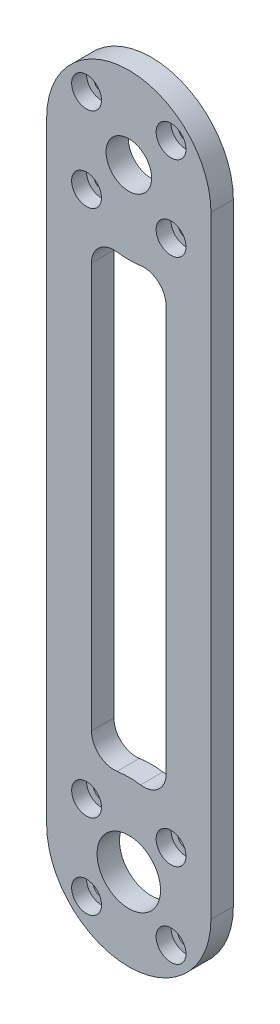
SolidWorks part; units mm, degrees
note: The reader was unsure of these and kept them because the rebuilt part matched: shared geometry of "Sketch3<6>", "Sketch2<5>".
ref_plane "Front Plane" through (0, 0, 0) normal (0, 0, 1) x (1, 0, 0)
ref_plane "Top Plane" through (0, 0, 0) normal (0, 1, 0) x (1, 0, 0)
ref_plane "Right Plane" through (0, 0, 0) normal (1, 0, 0) x (0, 0, -1)
sketch "Sketch1" plane through (0, 0, 0) normal (0, 0, 1) x (1, 0, 0)
  line L0 (0, 41) -> (0, -41) construction
  line L2 (11, 41) -> (11, -41)
  line L4 (-11, 41) -> (-11, -41)
  line L7 (-5, 31.202) -> (-5, -31.202)
  line L9 (5, 31.202) -> (5, -31.202)
  circle A0 centre (0, 41) radius 11
  circle A1 centre (0, -41) radius 11
  point P0 (0, 0)
  point P2 (0, 0)
  dimension "D3" = 22
  dimension "D1" = 82
  dimension "D5" = 6
  dimension "D2" = 22
  dimension "D6" = 6
extrude "Boss-Extrude1" add sketch "Sketch1" along normal blind 3
sketch "Sketch2" plane through (0, 0, 3) normal (0, 0, 1) x (1, 0, 0)
  line L0 (0, 41) -> (5.6569, 46.6569) construction
  line L1 (11, 41) -> (11, -41) construction
  circle A0 centre (0, 41) radius 3.05
  circle A1 centre (5.6569, 46.6569) radius 1
  circle A2 centre (5.6569, 46.6569) radius 2
  dimension "D1" = 6.1
  dimension "D2" = 2
  dimension "D5" = 4
  dimension "D3" = 8
  dimension "D4" = 45
sketch "Sketch3" plane through (0, 0, 3) normal (0, 0, 1) x (1, 0, 0)
  line L0 (5.6569, -35.3431) -> (0, -41) construction
  line L1 (11, 41) -> (11, -41) construction
  circle A0 centre (0, -41) radius 4.25
  circle A1 centre (5.6569, -35.3431) radius 1.1
  circle A2 centre (5.6569, -35.3431) radius 2
  dimension "D2" = 8.5
  dimension "D3" = 2.2
  dimension "D5" = 4
  dimension "D1" = 45
  dimension "D4" = 8
extrude "Cut-Extrude3" cut sketch "Sketch3" against normal up to surface (3 mm away) up to face at (0, 0, 0)
extrude "Cut-Extrude4" cut sketch "Sketch3<6>" against normal offset from surface (2 mm away) 1 up to face at (4.25, -41, 0)
sketch "Sketch3<6>" plane through (0, 0, 3) normal (0, 0, 1) x (1, 0, 0) same geometry as "Sketch3"
pattern_circular "CirPattern3" count 4 over 360 about axis through (0, -41, 0) along (0, 0, 1) of "Cut-Extrude3", "Cut-Extrude4"
extrude "Cut-Extrude5" cut sketch "Sketch2" against normal up to surface (3 mm away) up to face at (-4.5569, -35.3431, 0)
extrude "Cut-Extrude6" cut sketch "Sketch2<5>" against normal offset from surface (2 mm away) 1 up to face at (6.6569, 46.6569, 0)
sketch "Sketch2<5>" plane through (0, 0, 3) normal (0, 0, 1) x (1, 0, 0) same geometry as "Sketch2"
pattern_circular "CirPattern4" count 4 over 360 about axis through (0, 41, 0) along (0, 0, 1) of "Cut-Extrude6", "Cut-Extrude5"
fillet "Fillet1" radius 3 4 edges at (-5, -31.202, 1.5) (5, -31.202, 1.5) (-5, 31.202, 1.5) (5, 31.202, 1.5)
move or copy body "Corpo-Mover/Copiar1" [suppressed]
